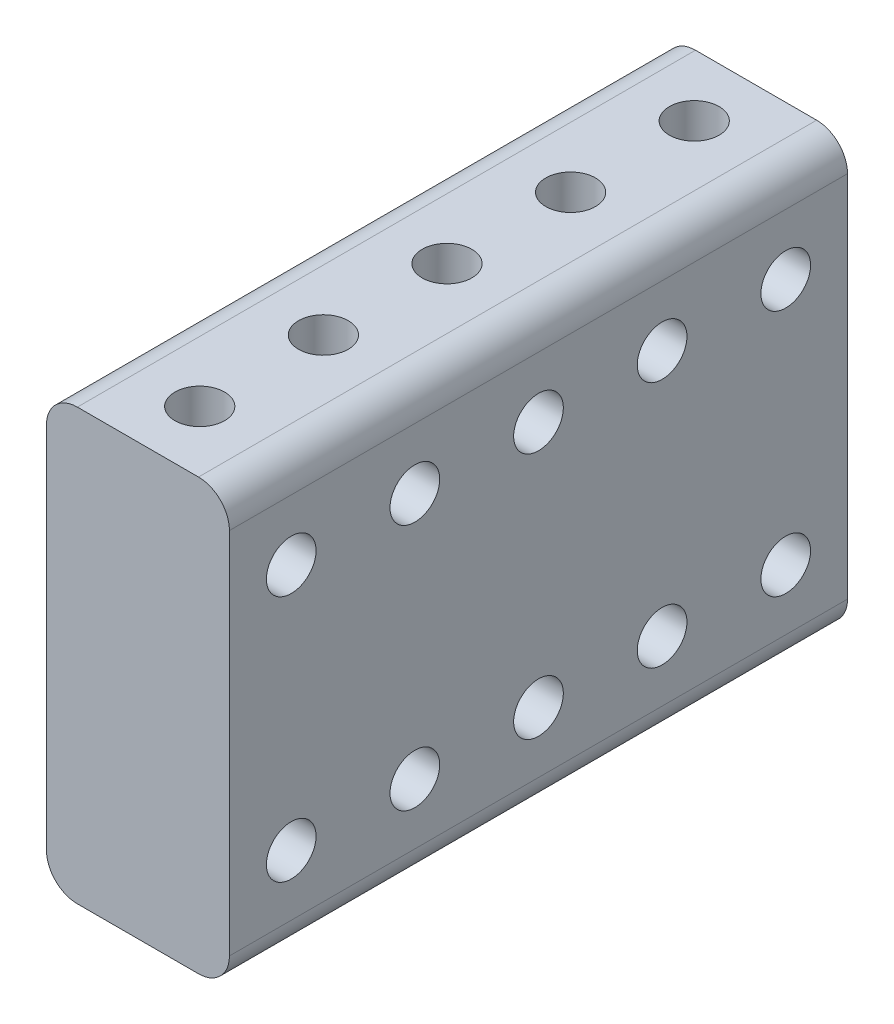
SolidWorks part; units mm, degrees
material "PET"
ref_plane "Front Plane" through (0, 0, 0) normal (0, 0, 1) x (1, 0, 0)
ref_plane "Top Plane" through (0, 0, 0) normal (0, 1, 0) x (1, 0, 0)
ref_plane "Right Plane" through (0, 0, 0) normal (1, 0, 0) x (0, 0, -1)
sketch "Sketch1" plane through (0, 0, 0) normal (0, 0, 1) x (1, 0, 0)
  line L1 (0, 0) -> (18.796, 0)
  line L2 (0, 0) -> (0, 44.196)
  line L3 (0, 44.196) -> (18.796, 44.196)
  line L4 (18.796, 0) -> (18.796, 44.196)
  dimension "D1" = 18.796
  dimension "D2" = 44.196
extrude "Boss-Extrude1" add sketch "Sketch1" along normal blind 63.5
fillet "Fillet1" radius 3.175 4 edges at (0, 44.196, 31.75) (18.796, 0, 31.75) (0, 0, 31.75) (18.796, 44.196, 31.75)
sketch "Sketch2" plane through (0, 44.196, 0) normal (0, 1, 0) x (1, 0, 0)
  line L0 (9.398, 0) -> (9.398, -63.5) construction
  line L1 (15.621, 0) -> (3.175, 0) construction
  line L2 (15.621, -63.5) -> (3.175, -63.5) construction
  circle A0 centre (9.398, -6.35) radius 2.5527
  circle A1 centre (9.398, -19.05) radius 2.5527
  circle A2 centre (9.398, -31.75) radius 2.5527
  circle A3 centre (9.398, -44.45) radius 2.5527
  circle A4 centre (9.398, -57.15) radius 2.5527
  dimension "D1" = 5.1054
  dimension "D4" = 12.7
  dimension "D2" = 6.35
  dimension "D3" = 5
extrude "Cut-Extrude1" cut sketch "Sketch2" against normal blind 63.5
sketch "Sketch3" plane through (18.796, 0, 0) normal (1, 0, 0) x (0, 0, -1)
  line L0 (-63.5, 22.098) -> (0, 22.098) construction
  line L1 (-63.5, 3.175) -> (-63.5, 41.021) construction
  line L2 (0, 3.175) -> (0, 41.021) construction
  circle A0 centre (-57.15, 34.798) radius 2.5527
  circle A1 centre (-44.45, 34.798) radius 2.5527
  circle A2 centre (-31.75, 34.798) radius 2.5527
  circle A3 centre (-19.05, 34.798) radius 2.5527
  circle A4 centre (-6.35, 34.798) radius 2.5527
  circle A5 centre (-44.45, 9.398) radius 2.5527
  circle A6 centre (-31.75, 9.398) radius 2.5527
  circle A7 centre (-19.05, 9.398) radius 2.5527
  circle A8 centre (-6.35, 9.398) radius 2.5527
  circle A9 centre (-57.15, 9.398) radius 2.5527
  dimension "D2" = 5.1054
  dimension "D3" = 6.35
  dimension "D1" = 12.7
  dimension "D6" = 25.4
  dimension "D7" = 12.7
  dimension "D4" = 5
  dimension "D5" = 2
extrude "Cut-Extrude2" cut sketch "Sketch3" against normal blind 63.5
